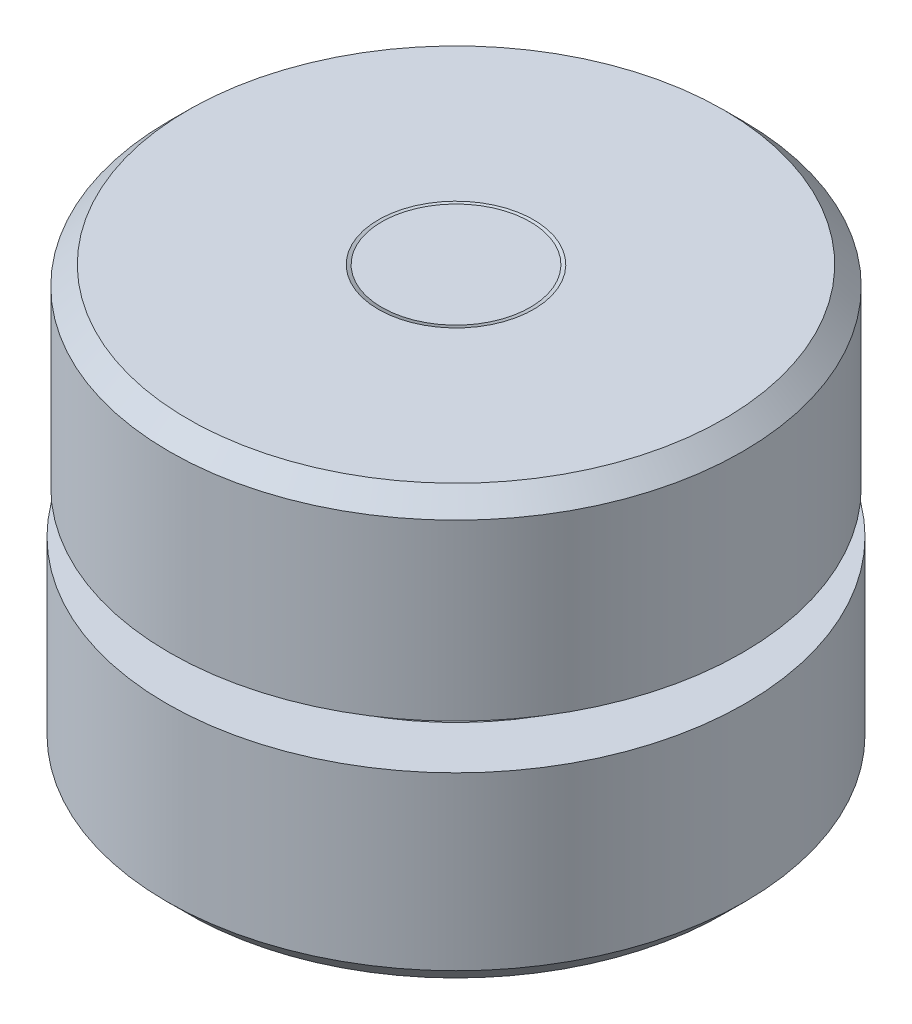
SolidWorks part; units mm, degrees
ref_plane "Front Plane" through (0, 0, 0) normal (0, 0, 1) x (1, 0, 0)
ref_plane "Top Plane" through (0, 0, 0) normal (0, 1, 0) x (1, 0, 0)
ref_plane "Right Plane" through (0, 0, 0) normal (1, 0, 0) x (0, 0, -1)
sketch "Layout" plane through (0, 0, 0) normal (0, 1, 0) x (1, 0, 0)
  circle A0 centre (0, 0) radius 21.4312 construction
  circle A1 centre (0, 0) radius 21.2328 construction
  point P3 (-21.4312, 0)
  point P4 (21.4312, 0)
  point P5 (0, 21.4312)
  point P6 (0, -21.4312)
  point P8 (21.2328, 0)
  point P9 (-21.2328, 0)
  point P13 (0, 0)
  dimension "OD" = 42.8625
  dimension "OD2" = 42.4656
sketch "Sketch1" plane through (0, 0, 0) normal (1, 0, 0) x (0, 0, -1)
  line L0 (-10.7156, 0) -> (10.7156, 0) construction
  line L1 (0, -15.875) -> (0, 15.875) construction
  line L2 (-19.8437, 15.875) -> (0, 15.875)
  line L3 (-16.864, 1.5875) -> (-21.4312, 1.5875)
  line L4 (-21.4312, 1.5875) -> (-21.4312, 14.2875)
  line L5 (-21.4312, 14.2875) -> (-19.8437, 15.875)
  line L6 (0, 15.875) -> (0, 1.5875)
  line L7 (0, 1.5875) -> (-4.5673, 1.5875)
  line L8 (-10.7156, 6.35) -> (-10.7156, 0) construction
  line L9 (-17.0656, 0) -> (-21.4312, 0) construction
  line L10 (0, -15.875) -> (0, -1.5875)
  line L11 (0, -1.5875) -> (-4.5673, -1.5875)
  line L12 (-16.864, -1.5875) -> (-21.4312, -1.5875)
  line L13 (-21.4312, -1.5875) -> (-21.4312, -14.2875)
  line L14 (-21.4312, -14.2875) -> (-19.8437, -15.875)
  line L15 (-19.8437, -15.875) -> (0, -15.875)
  circle A0 centre (-10.7156, 0) radius 6.35 construction
  arc A1 (-4.5673, 1.5875) -> (-16.864, 1.5875) centre (-10.7156, 0) ccw
  arc A2 (-4.5673, -1.5875) -> (-16.864, -1.5875) centre (-10.7156, 0) cw
  point P15 (-21.4312, 15.875)
  point P17 (-21.4312, -15.875)
  dimension "D2" = 12.7
  dimension "D1" = 45
  dimension "D4" = 1.5875
  dimension "D3" = 3.175
  dimension "D5" = 21.4312
  dimension "Th" = 31.75
revolve "Revolve1" add sketch "Sketch1" angle 360 about L1
sketch "Sketch3" plane through (0, 0, 0) normal (1, 0, 0) x (0, 0, -1)
  line L0 (-10.7156, 6.35) -> (-10.7156, -6.35)
  arc A0 (-16.864, -1.5875) -> (-4.5673, -1.5875) centre (-10.7156, 0) ccw construction
  arc A1 (-10.7156, 6.35) -> (-10.7156, -6.35) centre (-10.7156, 0) ccw
revolve "Revolve2" add sketch "Sketch3" angle 360 about L0
ref_axis "Axis1" through (0, 15.875, 0) along (0, -1, 0)
pattern_circular "CirPattern1" count 4 every 90 about axis through (0, 15.875, 0) along (0, -1, 0) of bodies 171
sketch "Sketch4" plane through (0, 0, 0) normal (1, 0, 0) x (0, 0, -1)
  line L0 (-5.7533, 15.875) -> (-3.0036, 14.2875)
  line L1 (-19.8437, 15.875) -> (0, 15.875) construction
  line L2 (-3.0036, 14.2875) -> (-3.0036, -14.2875)
  line L3 (-3.0036, -14.2875) -> (-5.7533, -15.875)
  line L4 (-19.8437, -15.875) -> (0, -15.875) construction
  line L5 (-5.7533, -15.875) -> (-5.4993, -15.875)
  line L6 (-5.4993, -15.875) -> (-2.8766, -14.3608)
  line L7 (-2.8766, -14.3608) -> (-2.8766, 14.3608)
  line L8 (-2.8766, 14.3608) -> (-5.4993, 15.875)
  line L9 (-5.4993, 15.875) -> (-5.7533, 15.875)
  line L10 (21.4312, 14.2875) -> (-21.4312, 14.2875) construction
  line L11 (0, 15.875) -> (-2.7496, 14.2875) construction
  line L12 (-2.8766, 14.3608) -> (-0.254, 15.875) construction
  dimension "D1" = 0.127
  dimension "D2" = 60
  dimension "D3" = 0.127
  dimension "D4" = 0.127
revolve "Cut-Revolve1" cut sketch "Sketch4" angle 360 about L6
sketch "Sketch5" plane through (0, 0, 0) normal (1, 0, 0) x (0, 0, -1)
  line L0 (0, -15.875) -> (0, 15.875) construction
  line L1 (5.4993, 15.875) -> (-5.4993, 15.875) construction
  line L3 (-21.4312, 1.5875) -> (-21.2328, 1.5875)
  line L4 (-21.4312, 1.5875) -> (-21.4312, 15.875)
  line L5 (-21.4312, 15.875) -> (-21.2328, 15.875)
  line L6 (-21.2328, 1.5875) -> (-21.2328, 15.875)
  point P6 (0, 0)
  dimension "D1" = 42.4656
revolve "Cut-Revolve2" cut sketch "Sketch5" angle 360 about L0
ref_axis "Center Axis 1" through (0, 14.978, 0) along (0, -1, 0)
ref_plane "Contact Plane 1" through (0, 15.875, 0) normal (0, 1, 0) x (1, 0, 0)
ref_plane "Contact Plane 2" through (0, -15.875, 0) normal (0, -1, 0) x (-1, 0, 0)
equation "\"D2@Sketch1\" = \"Th@Sketch1\" / 2.5"
equation "\"Angle@CirPattern1\" = 360/\"Balls@CirPattern1\""
equation "\"D4@Sketch1\" = \"Th@Sketch1\" * .05"
equation "\"D3@Sketch1\" = \"D2@Sketch1\"/4"
equation "\"D5@Sketch1\"=\"OD@Layout\"/2"
equation "\"D1@Sketch5\"=\"OD2@Layout\""
